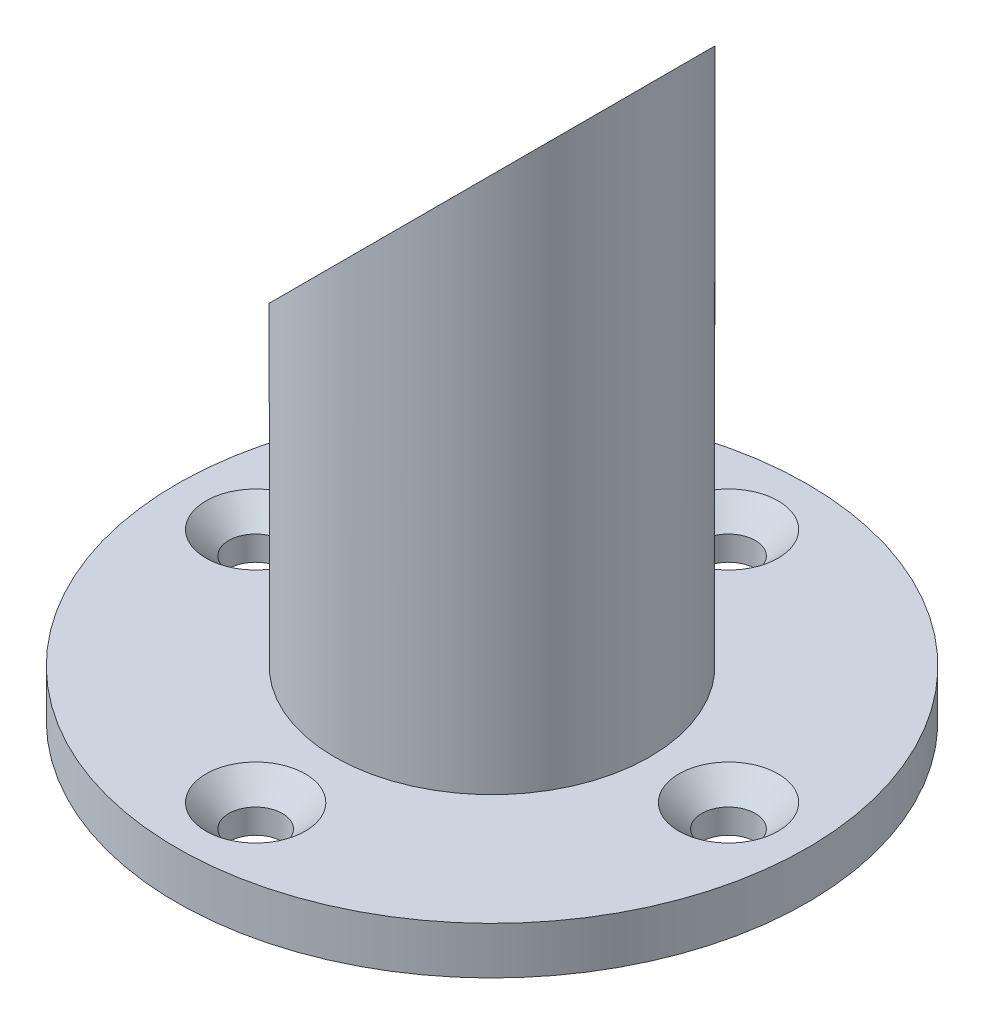
SolidWorks part; units mm, degrees
ref_plane "Front Plane" through (0, 0, 0) normal (0, 0, 1) x (1, 0, 0)
ref_plane "Top Plane" through (0, 0, 0) normal (0, 1, 0) x (1, 0, 0)
ref_plane "Right Plane" through (0, 0, 0) normal (1, 0, 0) x (0, 0, -1)
sketch "Sketch1" plane through (0, 0, 0) normal (0, 1, 0) x (1, 0, 0)
  circle A0 centre (0, 0) radius 10
  dimension "D1" = 20
extrude "Boss-Extrude1" add sketch "Sketch1" along normal blind 40 contours A0
sketch "Sketch2" plane through (0, 0, 0) normal (0, -1, 0) x (1, 0, 0)
  circle A0 centre (0, 0) radius 20
  dimension "D1" = 40
extrude "Boss-Extrude2" add sketch "Sketch2" against normal blind 3
hole_wizard "CSK for M3 Countersunk Flat Head Screw1" positions "Sketch4" profile "Sketch3" countersink size "M3" standard "ISO" end condition through all
sketch "Sketch4" plane through (0, 3, 0) normal (0, 1, 0) x (1, 0, 0)
  point P0 (0, 15)
  dimension "D1" = 15
sketch "Sketch3" plane through (0, 3, -15) normal (1, 0, 0) x (0, 0, 1)
  line L0 (0, 0) -> (0, 3)
  line L1 (0, 3) -> (1.7, 3)
  line L2 (1.7, 3) -> (1.7, 1.45)
  line L3 (1.7, 1.45) -> (3.15, 0)
  line L5 (3.15, 0) -> (0, 0)
  line L6 (-1.7, 1.45) -> (-3.15, 0) construction
  line L11 (0, -6.35) -> (0, 107.95) construction
  dimension "Thru Hole Dia." = 3.4
  dimension "Thru Hole Depth" = 3
  dimension "Near C'Sink Dia." = 6.3
  dimension "Near C'Sink Angle" = 90
pattern_circular "CirPattern1" count 4 over 360 about axis through (0, 3, 0) along (0, -1, 0) of "CSK for M3 Countersunk Flat Head Screw1"
sketch "Sketch5" plane through (0, 0, 0) normal (0, 0, 1) x (1, 0, 0)
  line L0 (-10, 40) -> (10, 40)
  line L1 (10, 40) -> (-10, 20)
  line L2 (-10, 40) -> (-10, 3) construction
  line L3 (-10, 20) -> (-10, 40)
extrude "Cut-Extrude1" cut sketch "Sketch5" against normal through all both and the other way through all
ref_axis "Axis1" through (0, 40, 0) along (0, -1, 0)
ref_point "Point1"
hole_wizard "M6 Tapped Hole1" positions "Sketch7" profile "Sketch6" tap size "M6" standard "ISO"
sketch "Sketch7" plane through (-15, 15, 0) normal (-0.7071, 0.7071, 0) x (0.7071, 0.7071, 0)
  point P0 (21.2132, 0)
sketch "Sketch6" plane through (0, 30, 0) normal (0, 0, 1) x (-0.7071, -0.7071, 0)
  line L0 (0, 0) -> (0, 11.5022)
  line L1 (0, 11.5022) -> (2.5, 10)
  line L2 (2.5, 10) -> (2.5, 0)
  line L5 (2.5, 0) -> (0, 0)
  line L10 (0, 11.5022) -> (-2.5, 10) construction
  line L11 (0, -6.35) -> (0, 107.95) construction
  dimension "Tap Drill Dia." = 5
  dimension "Tap Drill Depth" = 10
  dimension "Drill Angle" = 118
cosmetic thread "Hole Thread1" parameters "D1"=10, "D2"=6
